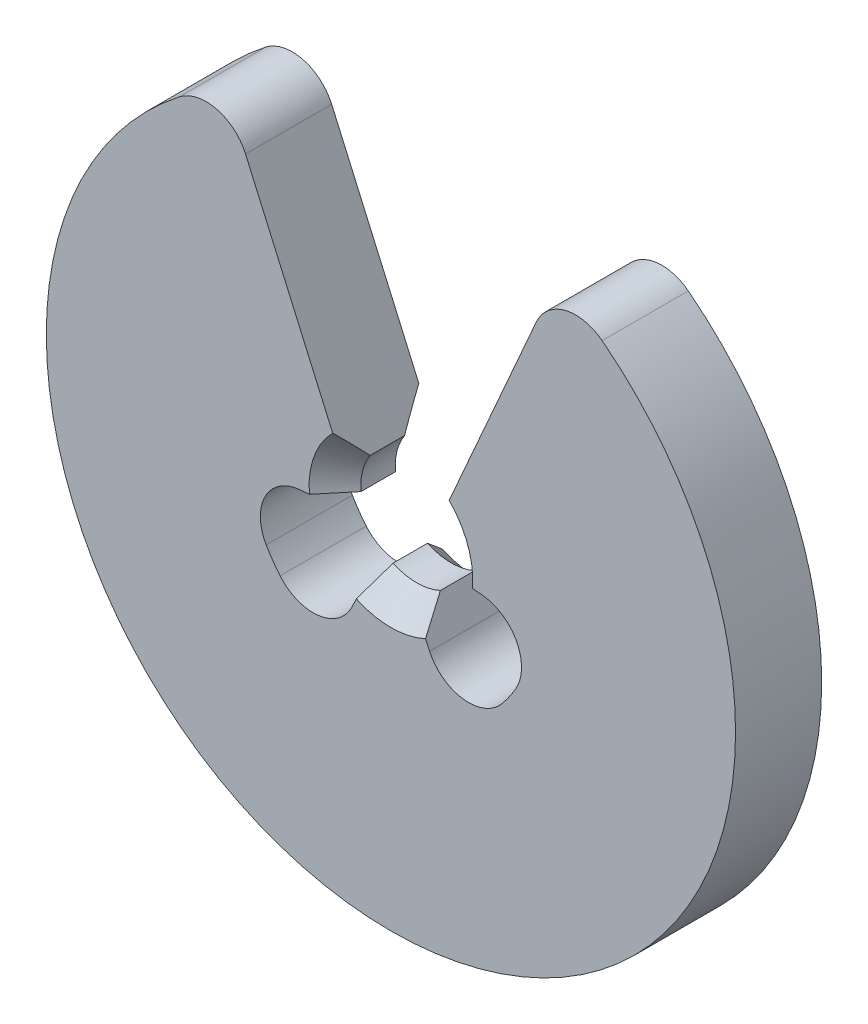
SolidWorks part; units mm, degrees
ref_plane "Front" through (0, 0, 0) normal (0, 0, 1) x (1, 0, 0)
ref_plane "Top" through (0, 0, 0) normal (0, 1, 0) x (1, 0, 0)
ref_plane "Right" through (0, 0, 0) normal (1, 0, 0) x (0, 0, -1)
sketch "Sketch1" plane through (0, 0, 0) normal (0, 0, 1) x (1, 0, 0)
  line L0 (0, 0) -> (0, 1.675) construction
  line L1 (0.98, 1.3584) -> (1.925, 3.5063)
  line L2 (-0.98, 1.3584) -> (-1.925, 3.5063)
  line L3 (0, 0) -> (1.675, 0) construction
  line L4 (1.675, 0) -> (4, 0) construction
  circle A0 centre (0, 0) radius 1.675 construction
  arc A1 (0.98, 1.3584) -> (-0.98, 1.3584) centre (0, 0) cw
  arc A2 (1.925, 3.5063) -> (-1.925, 3.5063) centre (0, 0) cw
  point P5 (1.8351, 2.4674)
  point P11 (0.9215, 1.2773)
  dimension "D1" = 3.35
  dimension "D2" = 4
  dimension "D4" = 0.25
extrude "Main Body" add sketch "Sketch1" along normal mid plane 1
sketch "Sketch2" plane through (0, 0, 0) normal (0, 0, 1) x (1, 0, 0)
  line L0 (0.98, 1.3584) -> (0.5409, 0.3604)
  line L1 (0.98, 1.3584) -> (1.925, 3.5063) construction
  line L2 (1.6686, -0.146) -> (0.6475, -0.0567)
  line L4 (0, 0) -> (0, 1.675) construction
  line L5 (-1.6686, -0.146) -> (-0.6475, -0.0567)
  line L6 (-0.98, 1.3584) -> (-0.5409, 0.3604)
  line L7 (0.7079, -1.5181) -> (0.2747, -0.5891)
  line L8 (-0.7079, -1.5181) -> (-0.2747, -0.5891)
  line L9 (0, 0) -> (0, 1.675) construction
  arc A0 (-0.5409, 0.3604) -> (-0.6475, -0.0567) centre (0, 0) ccw
  arc A1 (-0.98, 1.3584) -> (0.98, 1.3584) centre (0, 0) ccw construction
  arc A2 (0.6475, -0.0567) -> (0.5409, 0.3604) centre (0, 0) ccw
  arc A3 (-0.2747, -0.5891) -> (0.2747, -0.5891) centre (0, 0) ccw
  circle A4 centre (0, 0) radius 1.675 construction
  arc A5 (1.6686, -0.146) -> (0.98, 1.3584) centre (0, 0) ccw
  arc A6 (-0.7079, -1.5181) -> (0.7079, -1.5181) centre (0, 0) ccw
  arc A7 (-0.98, 1.3584) -> (-1.6686, -0.146) centre (0, 0) ccw
  point P4 (0.6656, -0.1333)
  dimension "D1" = 1.3
  dimension "D2" = 85
  dimension "D3" = 25
extrude "Teeth" add sketch "Sketch2" along normal through all and the other way through all
chamfer "Chamfer1" distance 0.3 angle 45 6 edges at (-0.6298, 0.1609, 0.5) (-0.6298, 0.1609, -0.5) (0, -0.65, 0.5) (0, -0.65, -0.5) (0.6298, 0.1609, 0.5) (0.6298, 0.1609, -0.5)
fillet "Fillet1" radius 0.5 6 edges at (1.6686, -0.146, 0) (0.7079, -1.5181, 0) (-0.7079, -1.5181, 0) (-1.6686, -0.146, 0) (1.925, 3.5063, 0) (-1.925, 3.5063, 0)
equation "\"D1@Sketch1\"=\"Hardware Clearance Hole Diameter@Box Assy.Assembly\"+.2"
